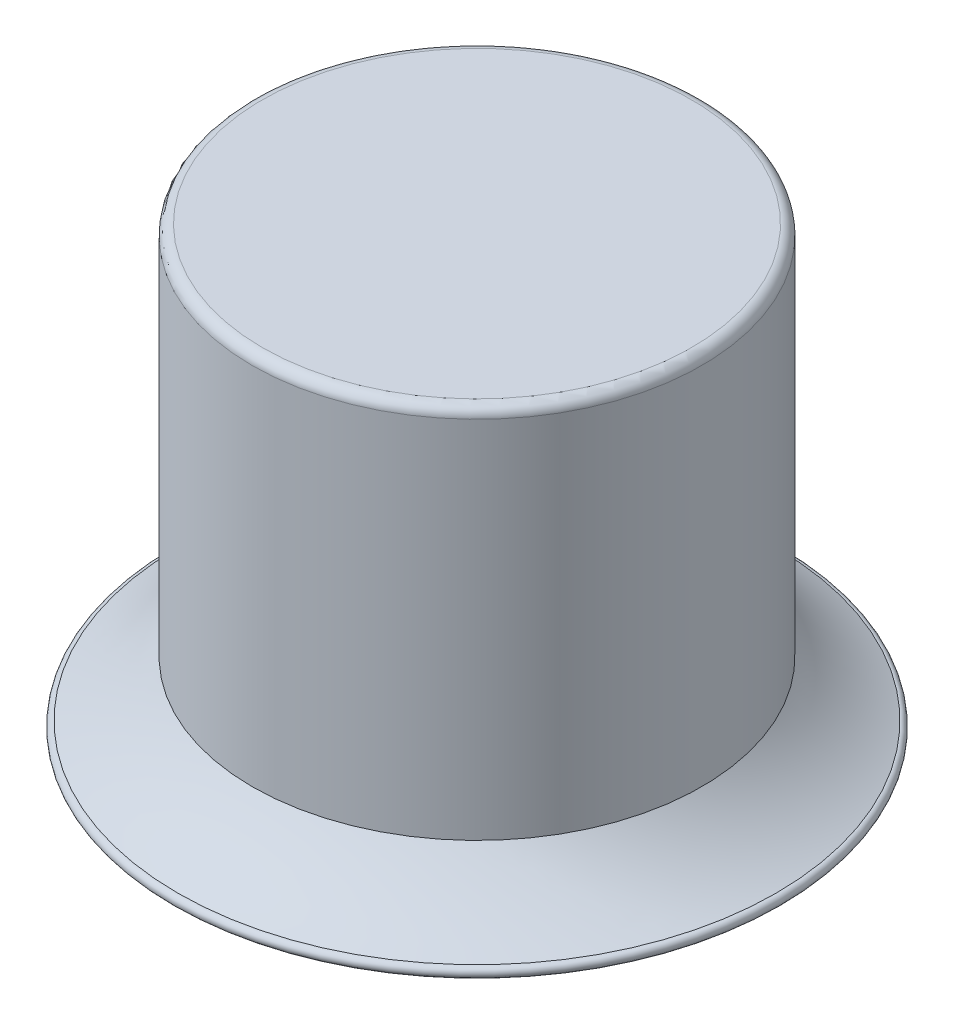
SolidWorks part; units mm, degrees
material "ABS"
ref_plane "Front Plane" through (0, 0, 0) normal (0, 0, 1) x (1, 0, 0)
ref_plane "Top Plane" through (0, 0, 0) normal (0, 1, 0) x (1, 0, 0)
ref_plane "Right Plane" through (0, 0, 0) normal (1, 0, 0) x (0, 0, -1)
sketch "Sketch1" plane through (0, 0, 0) normal (1, 0, 0) x (0, 0, -1)
  line L0 (0, 42) -> (0, 0) construction
  line L1 (0, 0) -> (28.5, 0) construction
  line L2 (21.4202, 6.2476) -> (21.4202, 41.0006)
  line L3 (20.4202, 5.958) -> (20.4202, 41.0006)
  line L4 (20.4202, 41.0006) -> (0, 41.0006)
  line L5 (20.4534, 42) -> (0, 42)
  line L6 (0, 42) -> (0, 41.0006)
  arc A0 (28.5, 0) -> (28.5, 1) centre (28.5, 0.5) ccw
  arc A1 (28.5, 1) -> (21.4202, 6.2476) centre (37.2907, 20.2597) cw
  arc A2 (28.5, 0) -> (20.4202, 5.958) centre (36.2907, 19.0227) cw
  arc A3 (21.4202, 41.0006) -> (20.4534, 42) centre (20.4202, 41.0006) ccw
  dimension "D1" = 28.5
  dimension "D2" = 42
  dimension "D3" = 1
  dimension "D4" = 0.9994
  dimension "D5" = 1
  dimension "D6" = 1
revolve "Revolve1" add sketch "Sketch1" angle 360 about L0
